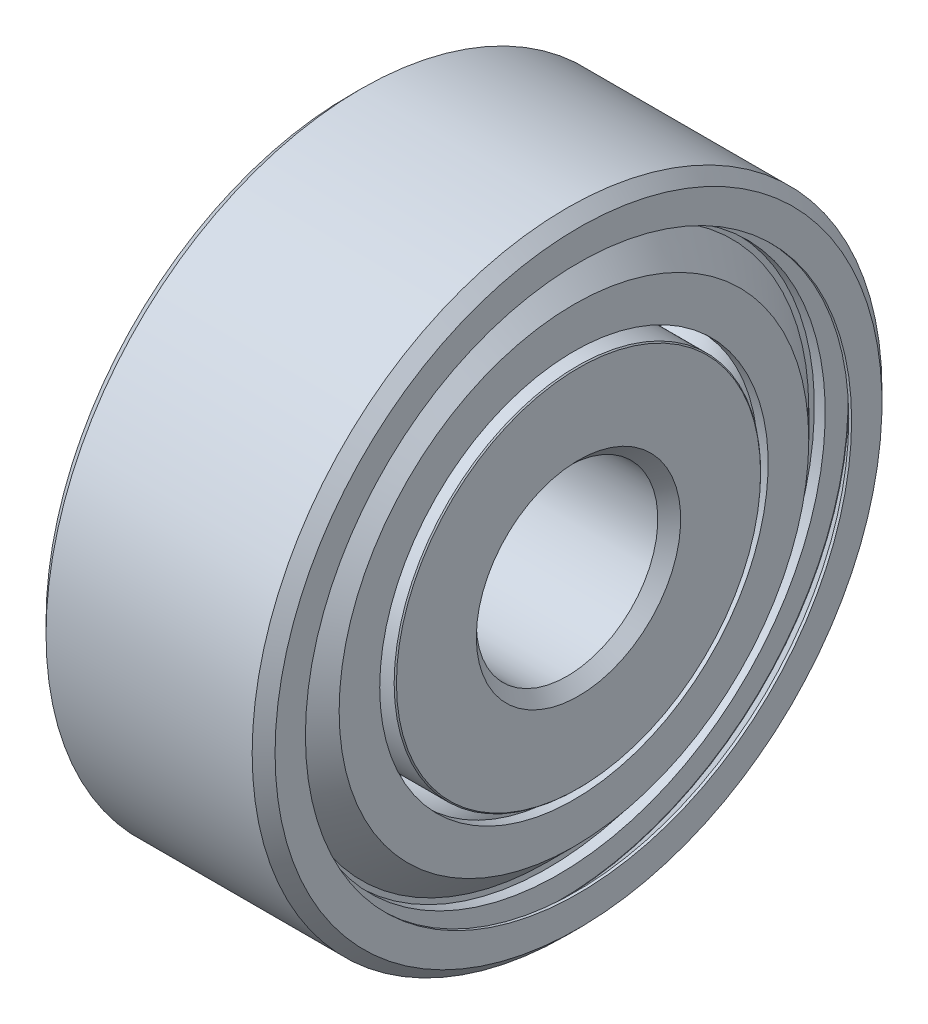
SolidWorks part; units mm, degrees
ref_plane "Front Plane" through (0, 0, 0) normal (0, 0, 1) x (1, 0, 0)
ref_plane "Top Plane" through (0, 0, 0) normal (0, 1, 0) x (1, 0, 0)
ref_plane "Right Plane" through (0, 0, 0) normal (1, 0, 0) x (0, 0, -1)
sketch "Sketch1" plane through (0, 0, 0) normal (0, 0, 1) x (1, 0, 0)
  line L0 (-2, 3.18) -> (-2, 1.785)
  line L1 (-1.8, 1.585) -> (1.8, 1.585)
  line L2 (2, 1.785) -> (2, 3.18)
  line L3 (1.98, 3.2) -> (1.0087, 3.2)
  line L4 (-1.98, 3.2) -> (-2, 3.18)
  line L5 (0, 0) -> (0, 26.3443) construction
  line L6 (-2, 1.785) -> (-1.8, 1.585)
  line L7 (1.8, 1.585) -> (2, 1.785)
  line L8 (2, 3.18) -> (1.98, 3.2)
  line L9 (0, 0) -> (38.1203, 0) construction
  line L10 (-2, 5.3) -> (-1.8, 5.5)
  line L11 (-1.25, 4.5) -> (-1.0087, 4.5)
  line L12 (-2, 4.77) -> (-2, 5.3)
  line L13 (-1.8, 5.5) -> (1.8, 5.5)
  line L14 (2, 4.77) -> (2, 5.3)
  line L15 (-2, 4.77) -> (-1.95, 4.77)
  line L16 (-1.95, 4.77) -> (-1.65, 5.07)
  line L17 (1.8, 5.5) -> (2, 5.3)
  line L18 (1.0087, 4.5) -> (1.25, 4.5)
  line L19 (-1.0087, 3.2) -> (-1.98, 3.2)
  line L20 (-1.65, 5.07) -> (-1.45, 5.07)
  line L21 (-1.45, 5.07) -> (-1.45, 4.77)
  line L22 (-1.45, 4.77) -> (-1.25, 4.77)
  line L23 (-1.25, 4.77) -> (-1.25, 4.5)
  line L24 (1.25, 4.77) -> (1.25, 4.5)
  line L25 (1.45, 4.77) -> (1.25, 4.77)
  line L26 (1.45, 5.07) -> (1.45, 4.77)
  line L27 (1.65, 5.07) -> (1.45, 5.07)
  line L28 (1.95, 4.77) -> (1.65, 5.07)
  line L29 (2, 4.77) -> (1.95, 4.77)
  line L30 (-1.447, 4.7565) -> (-1.447, 4.5746)
  line L31 (-1.6489, 5.0604) -> (-1.4589, 5.0604)
  line L32 (-1.6489, 5.0604) -> (-1.6489, 4.6604)
  line L33 (-1.6489, 4.6604) -> (-1.4589, 4.6604)
  line L34 (-1.4589, 5.0604) -> (-1.4589, 4.6604)
  line L35 (-1.447, 4.5746) -> (-1.9204, 4.1012)
  line L36 (-1.9204, 4.1012) -> (-1.9204, 3.3925)
  line L37 (-1.9204, 3.3925) -> (-1.7404, 3.3925)
  line L38 (-1.7404, 3.3925) -> (-1.7404, 4.0267)
  line L39 (-1.7404, 4.0267) -> (-1.267, 4.5)
  line L40 (-1.267, 4.5) -> (-1.267, 4.7565)
  line L41 (-1.267, 4.7565) -> (-1.447, 4.7565)
  line L42 (1.6489, 5.0604) -> (1.4589, 5.0604)
  line L43 (1.6489, 5.0604) -> (1.6489, 4.6604)
  line L44 (1.6489, 4.6604) -> (1.4589, 4.6604)
  line L45 (1.4589, 5.0604) -> (1.4589, 4.6604)
  line L46 (1.267, 4.7565) -> (1.447, 4.7565)
  line L47 (1.447, 4.7565) -> (1.447, 4.5746)
  line L48 (1.267, 4.5) -> (1.267, 4.7565)
  line L49 (1.7404, 4.0267) -> (1.267, 4.5)
  line L50 (1.447, 4.5746) -> (1.9204, 4.1012)
  line L51 (1.9204, 3.3925) -> (1.7404, 3.3925)
  line L52 (1.7404, 3.3925) -> (1.7404, 4.0267)
  line L53 (1.9204, 4.1012) -> (1.9204, 3.3925)
  line L54 (0, 5) -> (0, 2.7)
  arc A0 (-1.0087, 3.2) -> (1.0087, 3.2) centre (0, 3.85) ccw
  arc A1 (1.0087, 4.5) -> (-1.0087, 4.5) centre (0, 3.85) ccw
  circle A2 centre (0, 3.85) radius 1.15
  point P0 (-2, 3.2)
  point P1 (-2, 1.585)
  point P3 (2, 1.585)
  point P4 (2, 3.2)
  point P18 (-2, 4.5)
  point P19 (2, 5.5)
  point P20 (-2, 5.5)
  point P21 (2, 4.5)
  dimension "D11" = 1.2
  dimension "D25" = 2.3
  dimension "D1" = 1.585
  dimension "D2" = 4
  dimension "D7" = 3.2
  dimension "D8" = 0.05
  dimension "D9" = 5.5
  dimension "D12" = 45
  dimension "D10" = 0.65
  dimension "D14" = 0.2
  dimension "D15" = 0.2
  dimension "D17" = 4.77
  dimension "D18" = 0.3
  dimension "D19" = 4.5
  dimension "D20" = 0.19
  dimension "D21" = 0.4
  dimension "D22" = 0.18
  dimension "D23" = 0.18
  dimension "D24" = 45
revolve "Revolve1" add sketch "Sketch1" angle 360 about L9 region at (0, 2.3169, 0) region at (0, 5.1431, 0)
revolve "Revolve2" add sketch "Sketch1<3>" angle 360 about L9 region at (-1.357, 4.7414, 0) region at (1.357, 4.7414, 0)
sketch "Sketch1<3>" plane through (0, 0, 0) normal (0, 0, 1) x (1, 0, 0) same geometry as "Sketch1"
revolve "Revolve3" add sketch "Sketch1<4>" angle 360 about L9 region at (1.5539, 4.8604, 0)
sketch "Sketch1<4>" plane through (0, 0, 0) normal (0, 0, 1) x (1, 0, 0) same geometry as "Sketch1"
revolve "Revolve4" add sketch "Sketch1<5>" angle 360 about L54 region at (0.4881, 3.85, 0)
sketch "Sketch1<5>" plane through (0, 0, 0) normal (0, 0, 1) x (1, 0, 0) same geometry as "Sketch1"
pattern_circular "CirPattern2" count 8 over 360 about axis through (0, 0, 0) along (-1, 0, 0) of bodies 111
